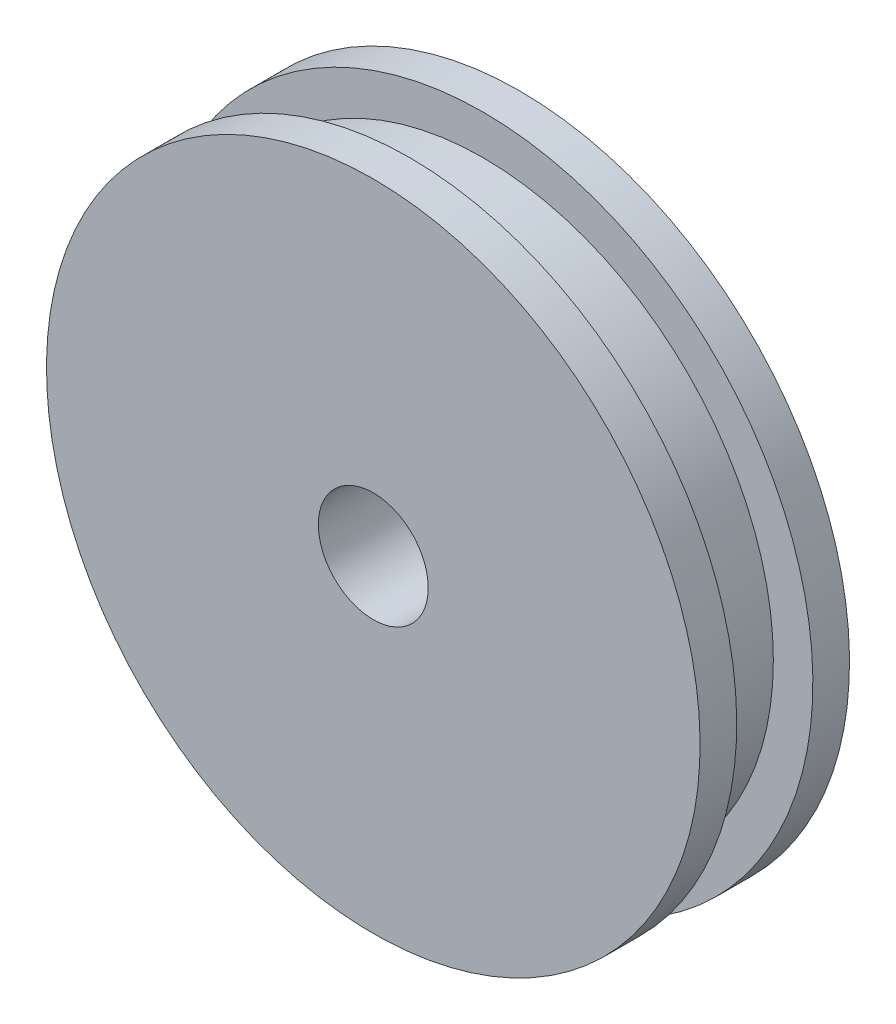
SolidWorks part; units mm, degrees
material "Настроенная пользователем пластмасса"
ref_plane "Спереди" through (0, 0, 0) normal (0, 0, 1) x (1, 0, 0)
ref_plane "Сверху" through (0, 0, 0) normal (0, 1, 0) x (1, 0, 0)
ref_plane "Справа" through (0, 0, 0) normal (1, 0, 0) x (0, 0, -1)
ref_plane "Плоскость4" through (0, 0, 0) normal (0, -1, 0) x (1, 0, 0)
sketch "Эскиз1" plane through (0, 0, 0) normal (0, -1, 0) x (1, 0, 0)
  line L0 (7.9208, 1) -> (7.9208, 3)
  line L1 (8.9208, 4) -> (1.5, 4)
  line L2 (1.5, 4) -> (1.5, 0)
  line L3 (1.5, 0) -> (9, 0)
  line L4 (7.9208, 3) -> (8.9208, 3)
  line L5 (0, 4) -> (0, 0) construction
  line L6 (8.9208, 3) -> (8.9208, 4)
  line L7 (7.9208, 1) -> (9, 1)
  line L8 (9, 1) -> (9, 0)
  dimension "D1" = 1
  dimension "D2" = 1
  dimension "D3" = 1
revolve "Повернуть1" add sketch "Эскиз1" angle 360 about L5 reverse direction yes
